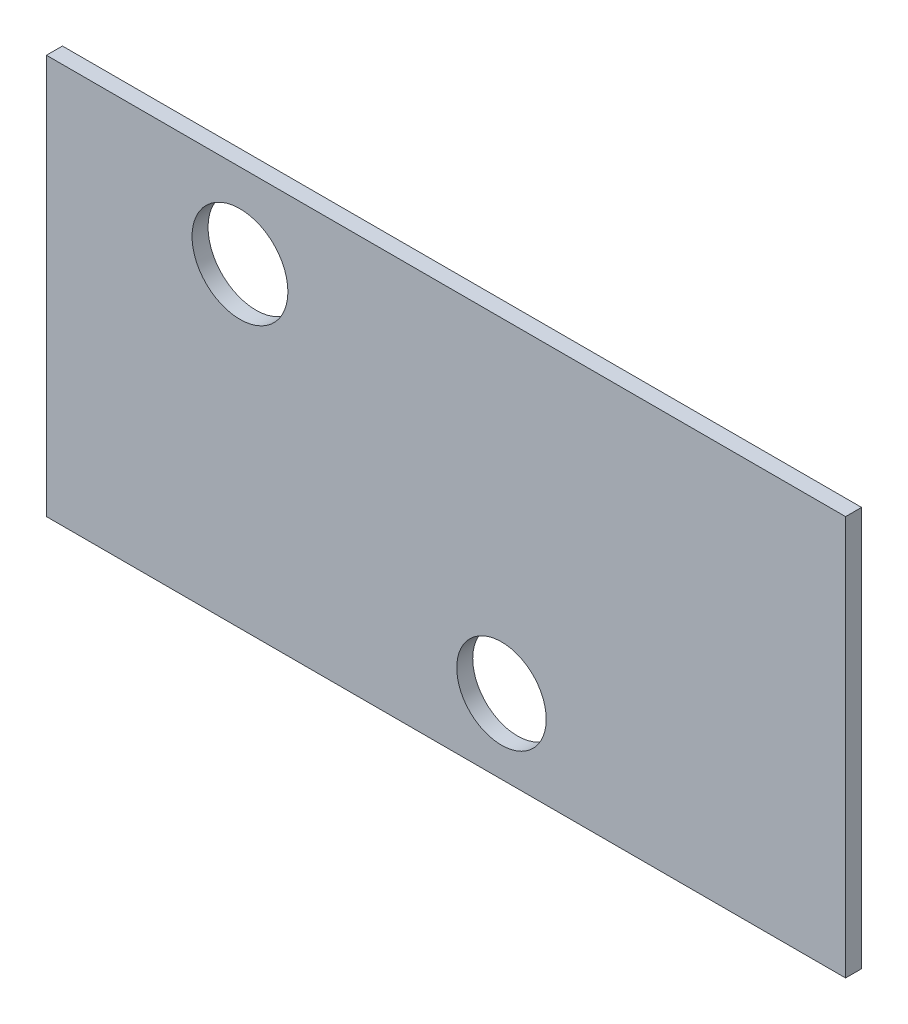
SolidWorks part; units mm, degrees
ref_plane "Front Plane" through (0, 0, 0) normal (0, 0, 1) x (1, 0, 0)
ref_plane "Top Plane" through (0, 0, 0) normal (0, 1, 0) x (1, 0, 0)
ref_plane "Right Plane" through (0, 0, 0) normal (1, 0, 0) x (0, 0, -1)
sketch "Sketch1" plane through (0, 0, 0) normal (0, 0, 1) x (1, 0, 0)
  line L1 (0, 0) -> (150, 0)
  line L2 (0, 0) -> (0, 75)
  line L3 (0, 75) -> (150, 75)
  line L4 (150, 0) -> (150, 75)
  dimension "D1" = 150
  dimension "D2" = 75
extrude "Boss-Extrude1" add sketch "Sketch1" along normal blind 3
sketch "Sketch2" plane through (0, 0, 3) normal (0, 0, 1) x (1, 0, 0)
  circle A0 centre (36.3279, 59.217) radius 8.9949
  circle A1 centre (85.4136, 13.9491) radius 8.4007
extrude "Cut-Extrude1" cut sketch "Sketch2" against normal blind 10
